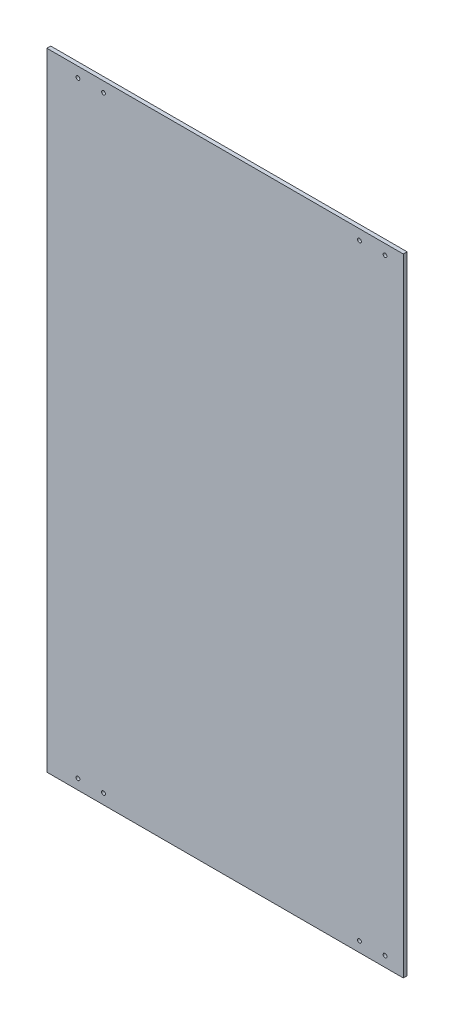
SolidWorks part; units mm, degrees
ref_plane "前视基准面" through (0, 0, 0) normal (0, 0, 1) x (1, 0, 0)
ref_plane "上视基准面" through (0, 0, 0) normal (0, 1, 0) x (1, 0, 0)
ref_plane "右视基准面" through (0, 0, 0) normal (1, 0, 0) x (0, 0, -1)
other "Configuration Table"
sketch "草图1" plane through (0, 0, 0) normal (0, 0, 1) x (1, 0, 0)
  line L0 (-99.3728, -240) -> (-123.3728, -240) construction
  line L1 (-139.28, 245) -> (139.28, 245)
  line L2 (-139.28, 245) -> (-139.28, -245)
  line L3 (-139.28, -245) -> (139.28, -245)
  line L4 (139.28, 245) -> (139.28, -245)
  line L5 (-139.28, 245) -> (139.28, -245) construction
  line L6 (-139.28, -245) -> (139.28, 245) construction
  line L7 (-52.7219, -240) -> (-100.7219, -240) construction
  line L8 (123.371, -240) -> (99.371, -240) construction
  line L9 (245.0535, 242) -> (105.7726, 242) construction
  line L10 (117.8123, -240) -> (128.3123, -240) construction
  line L11 (-123.3728, 242) -> (-99.3728, 242) construction
  line L12 (-100.7219, 242) -> (-52.7219, 242) construction
  line L13 (88.4521, 242) -> (105.7726, 242) construction
  circle A0 centre (104.9991, 237) radius 1.5
  circle A1 centre (124.9991, 237) radius 1.5
  circle A2 centre (-95.0009, 237) radius 1.5
  circle A3 centre (-115.0009, 237) radius 1.5
  circle A4 centre (124.9991, -237) radius 1.5
  circle A5 centre (104.9991, -237) radius 1.5
  circle A6 centre (-95.0009, -237) radius 1.5
  circle A7 centre (-115.0009, -237) radius 1.5
  point P0 (0, 0)
  point P16 (104.0666, -226.0713)
  point P23 (100.1824, -228.6712)
  point P26 (-148.3525, 249.1278)
  point P30 (0, 0)
  point P31 (0, 0)
  point P32 (0, 0)
  point P33 (0, 0)
  point P34 (0, 0)
  point P35 (0, 0)
  point P36 (0, 0)
  point P37 (0, 0)
  dimension "D3" = 24.2791
  dimension "D4" = 20
  dimension "D6" = 3
  dimension "D9" = 14.2809
  dimension "D1" = 490
  dimension "D2" = 278.56
  dimension "D5" = 3
  dimension "D7" = 3
  dimension "D8" = 20
  dimension "D10" = 3
  dimension "D11" = 24.2791
  dimension "D12" = 5
  dimension "D13" = 5
  dimension "D14" = 20
  dimension "D15" = 20
  dimension "D16" = 14.2809
  dimension "D17" = 5
  dimension "D18" = 5
extrude "凸台-拉伸1" add sketch "草图1" along normal blind 3
